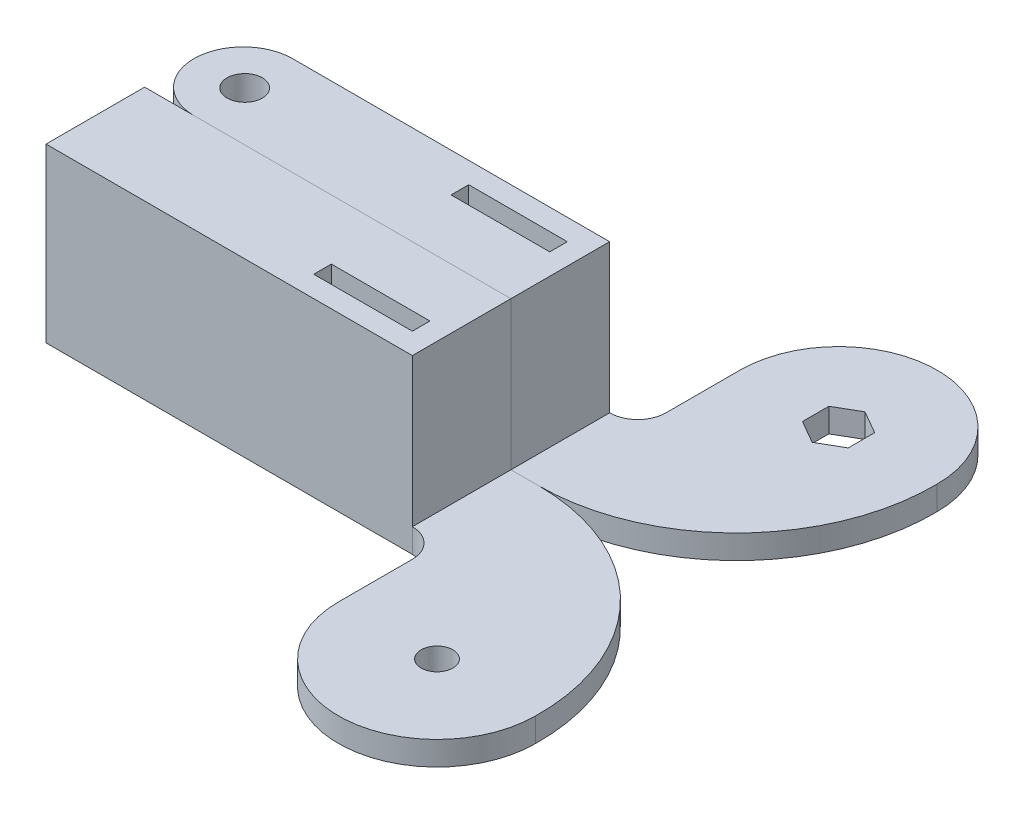
SolidWorks part; units mm, degrees
ref_plane "Front Plane" through (0, 0, 0) normal (0, 0, 1) x (1, 0, 0)
ref_plane "Top Plane" through (0, 0, 0) normal (0, 1, 0) x (1, 0, 0)
ref_plane "Right Plane" through (0, 0, 0) normal (1, 0, 0) x (0, 0, -1)
sketch "Эскиз1" plane through (0, 0, 0) normal (0, 1, 0) x (1, 0, 0)
  line L0 (-28, 0) -> (-28, 21)
  line L1 (-36, 29) -> (-140, 29)
  line L2 (-140, 29) -> (-140, 57)
  line L3 (-28, 0) -> (-28, 57)
  line L4 (-28, 57) -> (-140, 57)
  circle A0 centre (0, 0) radius 28
  arc A1 (28, 0) -> (-28, 57) centre (-28.1947, 0.8) ccw
  arc A2 (-36, 29) -> (-28, 21) centre (-36, 21) cw
  dimension "D1" = 56
  dimension "D4" = 56.2004
  dimension "D5" = 8
  dimension "D2" = 29
  dimension "D3" = 28
  dimension "D6" = 140
extrude "Бобышка-Вытянуть1" add sketch "Эскиз1" along normal blind 6.8 contours L1 A2 L3 L4 L2 | A0 A1 L3 L0 | A0 L3 region at (-8.1564, 0, -36.025) region at (0, 0, 0) region at (-83.7636, 0, -42.9312)
sketch "Эскиз3" plane through (0, 0, 0) normal (0, -1, 0) x (-1, 0, 0)
  circle A0 centre (0, 0) radius 4.5
  dimension "D1" = 9
extrude "Вырез-Вытянуть1" cut sketch "Эскиз3" against normal through all
sketch "Эскиз5" plane through (0, 6.8, 0) normal (0, 1, 0) x (1, 0, 0)
  line L1 (-36, 29) -> (-140, 29)
  line L2 (-36, 29) -> (-36, 57)
  line L3 (-36, 57) -> (-140, 57)
  line L4 (-140, 29) -> (-140, 57)
extrude "Бобышка-Вытянуть3" add sketch "Эскиз5" along normal blind 42.08
sketch "Эскиз6" plane through (0, 48.88, 0) normal (0, 1, 0) x (1, 0, 0)
  line L0 (-140, 29) -> (-36, 29) construction
  line L5 (-42, 51) -> (-70, 51)
  line L6 (-42, 51) -> (-42, 46)
  line L7 (-42, 46) -> (-70, 46)
  line L8 (-70, 51) -> (-70, 46)
  line L13 (-42, 35) -> (-70, 35)
  line L14 (-42, 35) -> (-42, 40)
  line L15 (-42, 40) -> (-70, 40)
  line L16 (-70, 35) -> (-70, 40)
  line L17 (-36, 57) -> (-140, 57) construction
  line L18 (-36, 29) -> (-36, 57) construction
  dimension "D5" = 5
  dimension "D6" = 5
  dimension "D7" = 6
  dimension "D8" = 6
  dimension "D9" = 6
  dimension "D10" = 6
  dimension "D13" = 28
  dimension "D14" = 28
extrude "Вырез-Вытянуть3" cut sketch "Эскиз6" against normal blind 6 contours L16 L13 L14 L15 region at (-56, 48.88, -37.5)
mirror "Зеркальное отражение1" about plane through (0, 6.8, -57) normal (0, 0, 1) of bodies 107
sketch "Эскиз7" plane through (0, 6.8, 0) normal (0, 1, 0) x (1, 0, 0)
  line L1 (0, 121.5) -> (-6.4952, 117.75)
  line L2 (-6.4952, 117.75) -> (-6.4952, 110.25)
  line L3 (-6.4952, 110.25) -> (0, 106.5)
  line L4 (0, 106.5) -> (6.4952, 110.25)
  line L5 (6.4952, 110.25) -> (6.4952, 117.75)
  line L6 (6.4952, 117.75) -> (0, 121.5)
  circle A0 centre (0, 114) radius 6.4952 construction
  dimension "D1" = 15
extrude "Вырез-Вытянуть4" cut sketch "Эскиз7" against normal through all
sketch "Эскиз8" plane through (0, 0, 0) normal (0, -1, 0) x (1, 0, 0)
  line L0 (-28, -57) -> (-140, -57) construction
  line L1 (-132.8, -63.8) -> (-118.4, -63.8)
  line L2 (-132.8, -63.8) -> (-132.8, -78.2)
  line L3 (-132.8, -78.2) -> (-118.4, -78.2)
  line L4 (-118.4, -63.8) -> (-118.4, -78.2)
  line L5 (-140, -85) -> (-140, -57) construction
  dimension "D1" = 14.4
  dimension "D2" = 14.4
  dimension "D3" = 6.8
  dimension "D4" = 7.2
extrude "Вырез-Вытянуть5" cut sketch "Эскиз8" against normal blind 14
sketch "Эскиз9" plane through (0, 14, 0) normal (0, -1, 0) x (1, 0, 0)
  line L0 (-125.6, -63.8) -> (-125.6, -78.2) construction
  line L1 (-118.4, -63.8) -> (-132.8, -63.8) construction
  line L2 (-132.8, -78.2) -> (-118.4, -78.2) construction
  line L3 (-125.6, -78.2) -> (-132.8, -71) construction
  line L4 (-132.8, -63.8) -> (-132.8, -78.2) construction
  line L5 (-132.8, -71) -> (-118.4, -71) construction
  line L6 (-118.4, -78.2) -> (-118.4, -63.8) construction
  circle A0 centre (-125.6, -71) radius 5
  point P14 (-125.6, -71)
extrude "Вырез-Вытянуть6" cut sketch "Эскиз9" against normal through all
fillet "Скругление1" radius 14 2 edges at (-140, 24.44, -85) (-140, 24.44, -57)
